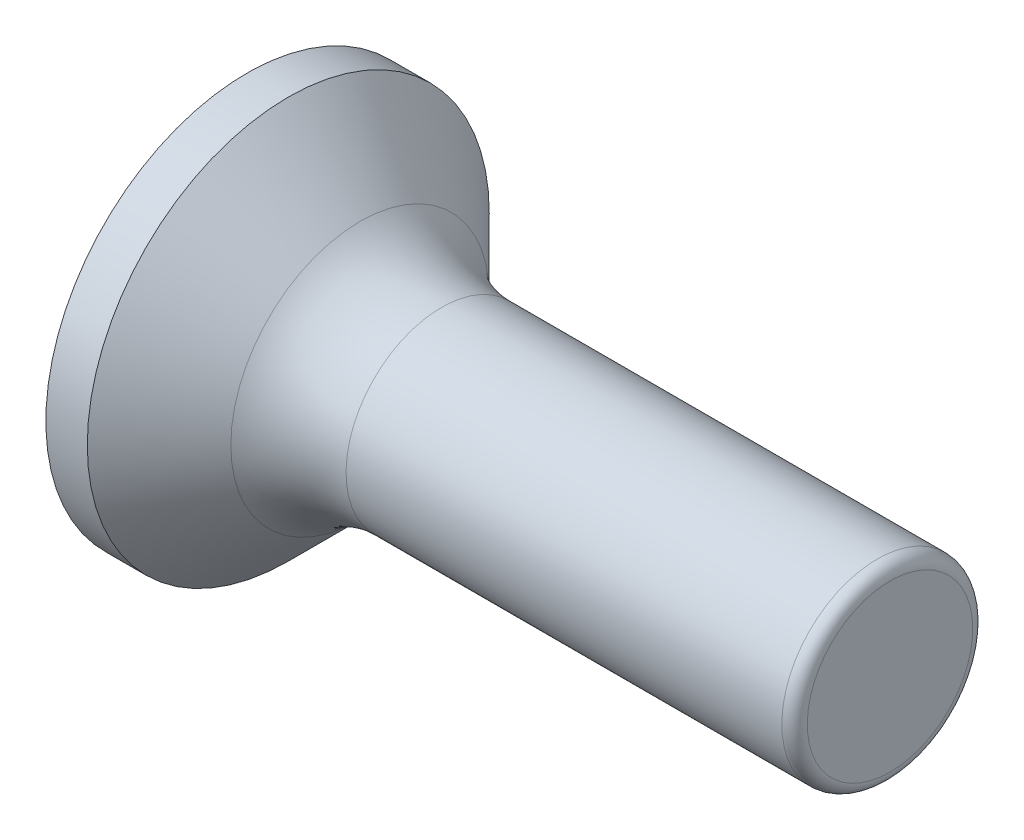
SolidWorks part; units mm, degrees
ref_plane "Front" through (0, 0, 0) normal (0, 0, 1) x (1, 0, 0)
ref_plane "Top" through (0, 0, 0) normal (0, 1, 0) x (1, 0, 0)
ref_plane "Right" through (0, 0, 0) normal (1, 0, 0) x (0, 0, -1)
sketch "Sketch1" plane through (0, 0, 0) normal (0, 0, 1) x (1, 0, 0)
  line L0 (-18.0939, 0) -> (12.9305, 0) construction
  line L1 (34.3, 0) -> (34.3, 4.75)
  line L2 (34.3, 4.75) -> (11.9851, 4.75)
  line L4 (4.36, 10) -> (2.3, 10)
  line L5 (34.3, 0) -> (0, 0)
  line L6 (7.9305, 6.4295) -> (4.36, 10)
  arc A0 (2.3, 10) -> (0, 0) centre (22.8891, 0) ccw
  arc A1 (7.9305, 6.4295) -> (11.9851, 4.75) centre (11.9851, 10.4841) ccw
  dimension "l" = 32
  dimension "D2" = 45
  dimension "k" = 5.6305
revolve "Base" add sketch "Sketch1" angle 360 about L0
cosmetic thread "ThreadCosmetic1" [suppressed] parameters "D1"=21.3695, "D2"=7.6
ref_plane "Plane1" through (0, 0, 0) normal (1, 0, 0) x (0, 0, -1)
sketch "Sketch2" plane through (0, 0, 0) normal (1, 0, 0) x (0, 0, -1)
  line L0 (6.5369, 0) -> (-7.0008, 0) construction
  line L1 (0, 6.811) -> (0, -6.4314) construction
  line L2 (-1.01, 5.05) -> (1.01, 5.05)
  line L3 (1.01, 5.05) -> (1.01, 1.01)
  line L4 (1.01, 1.01) -> (5.05, 1.01)
  line L5 (5.05, 1.01) -> (5.05, -1.01)
  line L6 (1.01, -1.01) -> (5.05, -1.01)
  line L7 (1.01, -5.05) -> (1.01, -1.01)
  line L8 (-1.01, -5.05) -> (1.01, -5.05)
  line L9 (-1.01, -5.05) -> (-1.01, -1.01)
  line L10 (-1.01, -1.01) -> (-5.05, -1.01)
  line L11 (-5.05, 1.01) -> (-5.05, -1.01)
  line L12 (-1.01, 1.01) -> (-5.05, 1.01)
  line L13 (-1.01, 5.05) -> (-1.01, 1.01)
  point P5 (-5.05, 0)
  point P11 (5.05, 0)
  point P15 (0, -5.05)
  point P20 (0, 5.05)
  dimension "D2" = 10.1
  dimension "D3" = 2.02
  dimension "D4" = 2.02
extrude "Cut-Extrude1" cut sketch "Sketch2" along normal blind 2.8153
draft "Draft1" type of draft neutral plane draft angle 45 neutral plane "Plane1" faces to draft 4 face at (1.6954, -5.05, 0) face at (1.6954, 0, -5.05) face at (1.6954, 0, 5.05) face at (1.6954, 5.05, 0) neutral plane through (0, 0, 0) neutral plane normal (1, 0, 0) reverse direction yes parameters "D1"=45
fillet "Fillet2" radius 0.6333 1 edges at (34.3, -4.75, 0)
sketch "Sketch3" plane through (0, 0, 0) normal (0, 0, 1) x (1, 0, 0)
  line L0 (12.4555, 5.7) -> (13.4055, 5.7)
  line L1 (13.4055, 5.7) -> (13.4055, 4.75)
  line L2 (13.4055, 4.75) -> (12.9305, 3.9273)
  line L3 (12.9305, 3.9273) -> (12.4555, 4.75)
  line L4 (12.4555, 4.75) -> (12.4555, 5.7)
  line L5 (0, 0) -> (18.7338, 0) construction
  line L6 (7.9305, -6.4295) -> (7.9305, 6.4295) construction
  dimension "D1" = 9.5
  dimension "D2" = 0.95
  dimension "D3" = 5
revolve "Cut-Revolve10" [suppressed] cut sketch "Sketch3" angle 360 about L5
pattern_linear "LPattern10" [suppressed] count 19 spacing 1.14 along (1, 0, 0) of bodies 103
equation "\"D3@Sketch2\" = \"m@Sketch2\" / 5"
equation "\"D4@Sketch2\" = \"D3@Sketch2\""
equation "\"D2@Sketch2\" = \"m@Sketch2\""
equation "\"D2@ThreadCosmetic1\" = \"st@Sketch1\"* 4 / 5"
equation "\"D1@Plane1\" = \"l@Sketch1\" + \"f@Sketch1\""
equation "\"qs@Cut-Extrude1\" = \"k@Sketch1\" / 2 "
equation "\"D1@Fillet2\" = \"st@Sketch1\" / 15"
equation "\"D1@ThreadCosmetic1\" = \"l@Sketch1\" - \"k@Sketch1\" - \"a@Sketch1\""
equation "\"D1@Sketch3\" = \"st@Sketch1\""
equation "\"D2@Sketch3\" = (  \"st@Sketch1\" - \"D2@ThreadCosmetic1\" )  / 2"
equation "\"D3@Sketch3\" = \"a@Sketch1\""
equation "\"D3@LPattern10\" = \"D2@Sketch3\" * 1.2"
equation "\"D1@LPattern10\" = \"D1@ThreadCosmetic1\" / \"D3@LPattern10\""
